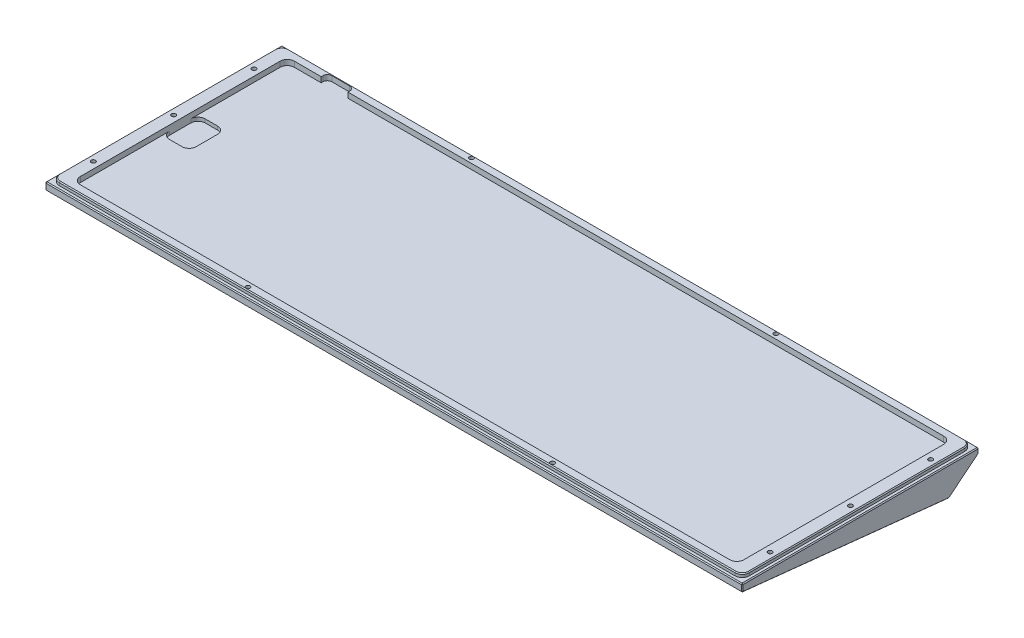
SolidWorks part; units mm, degrees
material "6061-T6 (SS)"
ref_plane "Front Plane" through (0, 0, 0) normal (0, 0, 1) x (1, 0, 0)
ref_plane "Top Plane" through (0, 0, 0) normal (0, 1, 0) x (1, 0, 0)
ref_plane "Right Plane" through (0, 0, 0) normal (1, 0, 0) x (0, 0, -1)
sketch "Sketch1" plane through (0, 0, 0) normal (0, 1, 0) x (1, 0, 0)
  line L1 (0, 0) -> (390.7, 0)
  line L2 (0, 0) -> (0, 132.7)
  line L3 (0, 132.7) -> (390.7, 132.7)
  line L4 (390.7, 0) -> (390.7, 132.7)
  dimension "D1" = 390.7
  dimension "D2" = 132.7
extrude "MainBody" add sketch "Sketch1" along normal blind 18.5
sketch "Sketch2" plane through (0, 18.5, 0) normal (0, 1, 0) x (1, 0, 0)
  line L0 (390.7, 132.7) -> (0, 132.7) construction
  line L1 (2, 130.7) -> (388.7, 130.7)
  line L2 (2, 130.7) -> (2, 2)
  line L3 (2, 2) -> (388.7, 2)
  line L4 (388.7, 130.7) -> (388.7, 2)
  line L5 (0, 132.7) -> (0, 0) construction
  line L7 (0, 132.7) -> (390.7, 132.7)
  line L8 (0, 132.7) -> (0, 0)
  line L9 (0, 0) -> (390.7, 0)
  line L10 (390.7, 132.7) -> (390.7, 0)
  point P4 (195.35, 130.7)
  point P7 (195.35, 132.7)
  point P8 (2, 66.35)
  point P11 (0, 66.35)
  line M5 (0, 132.7) -> (0, 0)
  line M6 (0, 0) -> (390.7, 0)
  line M7 (390.7, 0) -> (390.7, 132.7)
  line M8 (390.7, 132.7) -> (0, 132.7)
  dimension "D1" = 2
  dimension "D2" = 2
extrude "AligmentLip" cut sketch "Sketch2" against normal blind 2 contours L1 L4 L3 L2 M8 M5 M6 M7 region at (195.35, 18.5, -132.2874)
sketch "Sketch3" plane through (0, 0, 0) normal (-1, 0, 0) x (0, 0, 1)
  line L0 (-132.7, 13.5) -> (-116.0289, 0)
  line L1 (-132.7, 16.5) -> (-132.7, 0) construction
  line L2 (-132.7, 0) -> (0, 0) construction
  line L3 (-116.0289, 0) -> (0, 12.1951)
  line L4 (0, 16.5) -> (0, 0) construction
  line L5 (-132.7, 16.5) -> (0, 16.5) construction
  line L7 (-132.7, 16.5) -> (0, 16.5)
  line L8 (-132.7, 16.5) -> (-132.7, 0)
  line L9 (-132.7, 0) -> (0, 0)
  line L10 (0, 16.5) -> (0, 0)
  line M4 (-132.7, 16.5) -> (-132.7, 0)
  line M5 (-132.7, 0) -> (0, 0)
  line M6 (0, 0) -> (0, 16.5)
  dimension "D1" = 6
  dimension "D2" = 135
  dimension "D3" = 3
extrude "TypingAngle" cut sketch "Sketch3" against normal through all contours L0 M4 M5 | L3 M5 M6 region at (0, 4.5, -127.143) region at (0, 4.065, -38.6763)
sketch "Sketch4" plane through (0, 18.5, 0) normal (0, 1, 0) x (1, 0, 0)
  line L0 (2, 130.7) -> (388.7, 130.7) construction
  line L1 (9.35, 126.35) -> (381.35, 126.35)
  line L2 (9.35, 126.35) -> (9.35, 6.35)
  line L3 (9.35, 6.35) -> (381.35, 6.35)
  line L4 (381.35, 126.35) -> (381.35, 6.35)
  line L5 (2, 130.7) -> (2, 2) construction
  point P4 (195.35, 126.35)
  point P7 (195.35, 130.7)
  point P8 (9.35, 66.35)
  point P11 (2, 66.35)
  dimension "D1" = 372
  dimension "D2" = 120
extrude "PCBCutout" cut sketch "Sketch4" against normal blind 3
sketch "Sketch8" plane through (0, 18.5, 0) normal (0, 1, 0) x (1, 0, 0)
  line L0 (195.35, 132.7) -> (195.35, 0) construction
  line L1 (390.7, 132.7) -> (0, 132.7) construction
  line L2 (0, 0) -> (390.7, 0) construction
  line L3 (0, 66.35) -> (195.35, 66.35) construction
  line L4 (0, 132.7) -> (0, 0) construction
  line L5 (2, 130.7) -> (388.7, 130.7) construction
  line L6 (2, 2) -> (388.7, 2) construction
  line L7 (2, 130.7) -> (2, 2) construction
  point P11 (110, 129)
  point P12 (5.7, 111.35)
  point P13 (5.7, 66.35)
  point P14 (5.7, 21.35)
  point P16 (110, 3.7)
  point P27 (280.7, 3.7)
  point P28 (385, 21.35)
  point P29 (385, 66.35)
  point P30 (385, 111.35)
  point P31 (280.7, 129)
  dimension "D1" = 1.7
  dimension "D2" = 1.7
  dimension "D3" = 110
  dimension "D4" = 45
  dimension "D5" = 45
  dimension "D6" = 3.7
hole_wizard "M2 Clearance Hole2" positions "3DSketch7" profile "Sketch10" hole size "M2" standard "ANSI Metric" end condition through all
sketch3d "3DSketch7"
  point P0 (110, 18.5, -129)
  point P3 (5.7, 18.5, -111.35)
  point P6 (5.7, 18.5, -66.35)
  point P9 (5.7, 18.5, -21.35)
  point P12 (110, 18.5, -3.7)
  point P15 (280.7, 18.5, -129)
  point P18 (280.7, 18.5, -3.7)
  point P21 (385, 18.5, -21.35)
  point P24 (385, 18.5, -66.35)
  point P27 (385, 18.5, -111.35)
sketch "Sketch10" plane through (110, 18.5, -129) normal (1, 0, 0) x (0, 0, 1)
  line L0 (0, 0) -> (0, 18.5)
  line L1 (0, 18.5) -> (1.2, 18.5)
  line L2 (1.2, 18.5) -> (1.2, 0)
  line L5 (1.2, 0) -> (0, 0)
  line L11 (0, -6.35) -> (0, 107.95) construction
  dimension "Thru Hole Dia." = 2.4
  dimension "Thru Hole Depth" = 18.5
sketch "Sketch11" plane through (0, 15.5, 0) normal (0, 1, 0) x (1, 0, 0)
  line L0 (195.35, 132.7) -> (195.35, 0) construction
  line L1 (0, 0) -> (390.7, 0) construction
  circle A0 centre (110, 129) radius 2.5
  circle A1 centre (5.7, 111.35) radius 2.5
  circle A2 centre (5.7, 66.35) radius 2.5
  circle A3 centre (5.7, 21.35) radius 2.5
  circle A4 centre (110, 3.7) radius 2.5
  circle A5 centre (280.7, 3.7) radius 2.5
  circle A6 centre (385, 21.35) radius 2.5
  circle A7 centre (385, 66.35) radius 2.5
  circle A8 centre (385, 111.35) radius 2.5
  circle A9 centre (280.7, 129) radius 2.5
  dimension "D1" = 5
extrude "Cut-Extrude2" cut sketch "Sketch11" against normal through all from offset 1 offset against normal yes
sketch "Sketch12" plane through (0, 18.5, 0) normal (0, 1, 0) x (1, 0, 0)
  line L0 (381.35, 126.35) -> (9.35, 126.35) construction
  line L1 (28.4, 126.35) -> (43.4, 126.35)
  line L2 (28.4, 126.35) -> (28.4, 129.85)
  line L3 (28.4, 129.85) -> (43.4, 129.85)
  line L4 (43.4, 126.35) -> (43.4, 129.85)
  line L5 (0, 132.7) -> (0, 0) construction
  point P6 (35.9, 129.85)
  dimension "D1" = 15
  dimension "D2" = 3.5
  dimension "D3" = 35.9
extrude "Cut-Extrude3" cut sketch "Sketch12" against normal up to surface (3 mm away) up to face at (195.35, 15.5, -66.35)
fillet "Fillet1" radius 2.5 2 edges at (43.4, 17, -129.85) (28.4, 17, -129.85)
sketch "Sketch13" plane through (0, 15.5, 0) normal (0, 1, 0) x (1, 0, 0)
  line L0 (9.35, 126.35) -> (9.35, 6.35) construction
  line L1 (9.35, 76.35) -> (24.35, 76.35)
  line L2 (9.35, 76.35) -> (9.35, 56.35)
  line L3 (9.35, 56.35) -> (24.35, 56.35)
  line L4 (24.35, 76.35) -> (24.35, 56.35)
  line L5 (2, 130.7) -> (2, 2) construction
  point P6 (9.35, 66.35)
  point P9 (2, 66.35)
  dimension "D1" = 15
  dimension "D2" = 20
extrude "Cut-Extrude4" cut sketch "Sketch13" against normal blind 2
fillet "Fillet2" radius 4 12 edges at (381.35, 17, -126.35) (388.7, 17.5, -130.7) (388.7, 17.5, -2) (381.35, 17, -6.35) (9.35, 17, -6.35) (2, 17.5, -2) (9.35, 17, -126.35) (2, 17.5, -130.7) (9.35, 14.5, -56.35) (24.35, 14.5, -56.35) (9.35, 14.5, -76.35) (24.35, 14.5, -76.35)
sketch "Sketch17" plane through (0, 12.0619, -1.2678) normal (0, -0.9945, 0.1045) x (1, 0, 0)
  line L0 (198.6, -66.2253) -> (196.6, -66.2253) construction
  line L1 (198.6, -76.2253) -> (196.6, -76.2253)
  line L2 (198.6, -76.2253) -> (198.6, -56.2253)
  line L3 (198.6, -56.2253) -> (196.6, -56.2253)
  line L4 (196.6, -76.2253) -> (196.6, -56.2253)
  line L5 (203.1, -66.2253) -> (201.1, -66.2253)
  line L6 (203.1, -66.2253) -> (203.1, -48.7253)
  line L7 (203.1, -48.7253) -> (201.1, -48.7253)
  line L8 (201.1, -66.2253) -> (201.1, -48.7253)
  line L9 (194.1, -66.7253) -> (192.1, -66.7253)
  line L10 (194.1, -66.7253) -> (194.1, -56.7253)
  line L11 (194.1, -56.7253) -> (192.1, -56.7253)
  line L12 (192.1, -66.7253) -> (192.1, -56.7253)
  line L13 (189.6, -66.7253) -> (187.6, -66.7253)
  line L14 (189.6, -66.7253) -> (189.6, -56.7253)
  line L15 (189.6, -56.7253) -> (187.6, -56.7253)
  line L16 (187.6, -66.7253) -> (187.6, -56.7253)
  line L17 (185.1, -66.7253) -> (183.1, -66.7253)
  line L18 (185.1, -66.7253) -> (185.1, -56.7253)
  line L19 (185.1, -56.7253) -> (183.1, -56.7253)
  line L20 (183.1, -66.7253) -> (183.1, -56.7253)
  line L21 (208.1, -55.7253) -> (206.1, -55.7253)
  line L22 (208.1, -55.7253) -> (208.1, -48.2253)
  line L23 (208.1, -48.2253) -> (206.1, -48.2253)
  line L24 (206.1, -55.7253) -> (206.1, -48.2253)
  line L25 (203.1, -66.2253) -> (187.6, -66.2253) construction
  line L26 (390.7, -115.3933) -> (0, -115.3933) construction
  line L27 (202.1, -70.7253) -> (193.1, -70.7253)
  line L28 (202.1, -68.7253) -> (193.1, -68.7253)
  line L29 (390.7, 1.2747) -> (0, 1.2747) construction
  circle A0 centre (202.1, -69.7253) radius 1
  circle A2 centre (193.1, -69.7253) radius 1
  point P28 (195.35, -66.2253)
  point P29 (202.1, -66.2253)
  point P33 (195.35, -115.3933)
  point P39 (193.1, -66.7253)
  dimension "D12" = 2
  dimension "D13" = 17.5
  dimension "D1" = 20
  dimension "D2" = 2
  dimension "D3" = 3
  dimension "D4" = 2.5
  dimension "D5" = 2.5
  dimension "D6" = 2.5
  dimension "D7" = 2.5
  dimension "D8" = 10
  dimension "D9" = 0.5
  dimension "D10" = 0.5
  dimension "D11" = 3.5
  dimension "D14" = 7.5
  dimension "D15" = 50
extrude "Cut-Extrude7" cut sketch "Sketch17" against normal blind 1 contours L24 L21 L22 L23 | L8 L5 L6 L7 | L28 L2 L3 L4 | L12 L9 L10 L11 | L16 L13 L14 L15 | L20 L17 L18 L19 | A0 | L2 L28 L4 L27 | L2 L27 L4 L1 | A2 L27 L4 L28 | A2 L24 region at (197.6, 4.3816, -74.3405) region at (197.6, 4.7736, -70.6111) region at (195.2335, 4.7736, -70.6111) region at (197.6, 5.5314, -63.4008) region at (202.1, 4.7736, -70.6111) region at (193.1, 4.7736, -70.6111) region at (202.1, 6.0541, -58.4282) region at (193.1, 5.6098, -62.6549) region at (188.6, 5.6098, -62.6549) region at (184.1, 5.6098, -62.6549) region at (207.1, 6.629, -52.9583)
fillet "Fillet3" radius 1 24 edges at (183.1, 6.6297, -57.7345) (187.6, 6.6297, -57.7345) (192.1, 6.6297, -57.7345) (185.1, 6.6297, -57.7345) (189.6, 6.6297, -57.7345) (194.1, 6.6297, -57.7345) (185.1, 5.5845, -67.6798) (189.6, 5.5845, -67.6798) (194.1, 5.5845, -67.6798) (183.1, 5.5845, -67.6798) (187.6, 5.5845, -67.6798) (192.1, 5.5845, -67.6798) (196.6, 4.5914, -77.1277) (198.6, 4.5914, -77.1277) (196.6, 6.682, -57.2373) (198.6, 6.682, -57.2373) (201.1, 7.466, -49.7784) (203.1, 7.466, -49.7784) (206.1, 7.5182, -49.2811) (208.1, 7.5182, -49.2811) (208.1, 6.7343, -56.74) (206.1, 6.7343, -56.74) (201.1, 5.6367, -67.1825) (203.1, 5.6367, -67.1825)
chamfer "Chamfer1" distance 0.5 angle 45 13 edges at (195.35, 12.1951, 0) (390.7, 15, -132.7) (0, 15, -132.7) (0, 6.75, -124.3644) (390.7, 6.75, -124.3644) (390.7, 6.0976, -58.0144) (390.7, 14.3476, 0) (0, 6.0976, -58.0144) (0, 14.3476, 0) (0, 16.5, -66.35) (195.35, 16.5, 0) (390.7, 16.5, -66.35) (195.35, 16.5, -132.7) first distance on face at (195.35, 14.3476, 0) first distance on face at (195.35, 15, -132.7) first distance on face at (280.7, 12.5283, -131.5) first distance on face at (202.1, 4.6691, -71.6056) first distance on face at (0, 11.739, -76.2858) first distance on face at (390.7, 11.739, -76.2858)
chamfer "Chamfer2" distance 0.5 angle 45 8 edges at (388.7, 18.5, -66.35) (387.5284, 18.5, -129.5284) (387.5284, 18.5, -3.1716) (195.35, 18.5, -130.7) (195.35, 18.5, -2) (3.1716, 18.5, -129.5284) (3.1716, 18.5, -3.1716) (2, 18.5, -66.35)
